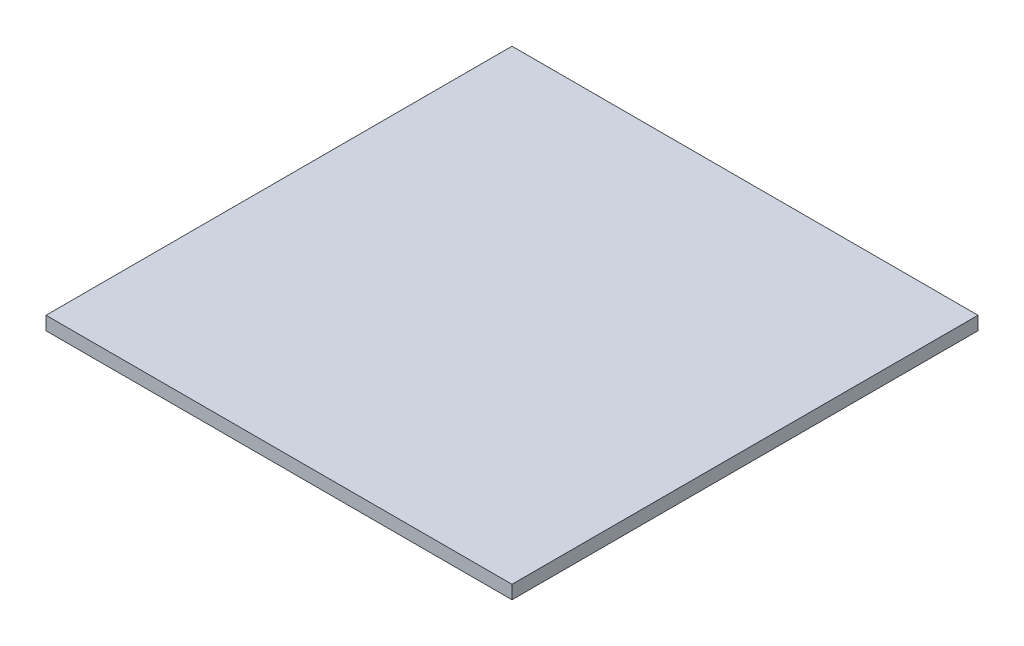
SolidWorks part; units mm, degrees
ref_plane "Front Plane" through (0, 0, 0) normal (0, 0, 1) x (1, 0, 0)
ref_plane "Top Plane" through (0, 0, 0) normal (0, 1, 0) x (1, 0, 0)
ref_plane "Right Plane" through (0, 0, 0) normal (1, 0, 0) x (0, 0, -1)
sketch "Sketch1" plane through (0, 0, 0) normal (0, 1, 0) x (1, 0, 0)
  line L1 (520, 520) -> (-520, 520)
  line L2 (520, 520) -> (520, -520)
  line L3 (520, -520) -> (-520, -520)
  line L4 (-520, 520) -> (-520, -520)
  line L5 (520, 520) -> (-520, -520) construction
  line L6 (520, -520) -> (-520, 520) construction
  point P0 (0, 0)
  dimension "D1" = 1040
  dimension "D2" = 1040
extrude "Boss-Extrude1" add sketch "Sketch1" along normal blind 30
